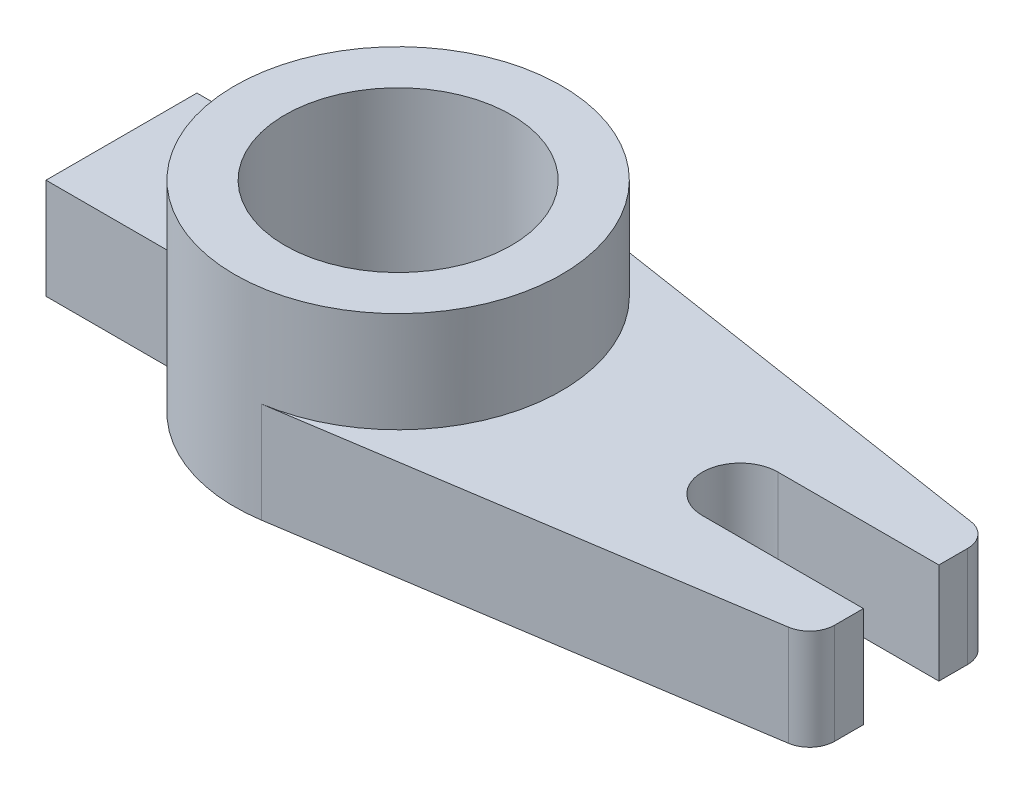
SolidWorks part; units mm, degrees
ref_plane "Front Plane" through (0, 0, 0) normal (0, 0, 1) x (1, 0, 0)
ref_plane "Top Plane" through (0, 0, 0) normal (0, 1, 0) x (1, 0, 0)
ref_plane "Right Plane" through (0, 0, 0) normal (1, 0, 0) x (0, 0, -1)
sketch "Sketch2" plane through (0, 0, 0) normal (0, 1, 0) x (1, 0, 0)
  line L0 (-56.2668, 0) -> (268.8737, 0) construction
  line L1 (-28.8314, 15) -> (-55, 15)
  line L2 (-28.8314, -15) -> (-55, -15)
  line L3 (-55, 15) -> (-55, -15)
  line L4 (4.9411, 32.1222) -> (95.7602, 18.1522)
  line L5 (4.9411, -32.1222) -> (95.7602, -18.1522)
  line L6 (68, 7.5) -> (100, 7.5)
  line L7 (68, -7.5) -> (100, -7.5)
  line L8 (100, 7.5) -> (100, 13.2103)
  line L9 (100, -7.5) -> (100, -13.2103)
  circle A0 centre (0, 0) radius 22.5
  circle A1 centre (0, 0) radius 32.5
  circle A5 centre (68, 0) radius 7.5
  arc A6 (100, -13.2103) -> (95.7602, -18.1522) centre (95, -13.2103) cw
  arc A7 (100, 13.2103) -> (95.7602, 18.1522) centre (95, 13.2103) ccw
  point P13 (99.6342, -9.4126)
  point P16 (99.6342, 9.6982)
  point P24 (100, -17.5)
  point P27 (100, 17.5)
  dimension "D1" = 65
  dimension "D2" = 45
  dimension "D5" = 15
  dimension "D6" = 0
  dimension "D7" = 35
  dimension "D8" = 32
  dimension "D9" = 5
  dimension "D3" = 30
  dimension "D4" = 55
  dimension "D10" = 100
extrude "Boss-Extrude1" add sketch "Sketch2" along normal blind 20 contours A1 L0 A5 L6 L8 A7 L4 | L0 A1 L5 A6 L9 L7 A5 | L0 L3 L2 A1 | L3 L0 A1 L1 region at (55.8895, 0, -14.3822) region at (55.8895, 0, 14.3822) region at (-43.1283, 0, 7.6911) region at (-43.1283, 0, -7.6911)
extrude "Boss-Extrude2" add sketch "Sketch2<3>" along normal blind 40 contours A1 L0 A0 | L0 A1 A0 region at (0, 0, -23.2267) region at (27.5, 0, 0.7267)
sketch "Sketch2<3>" plane through (0, 0, 0) normal (0, 1, 0) x (1, 0, 0) same geometry as "Sketch2"
